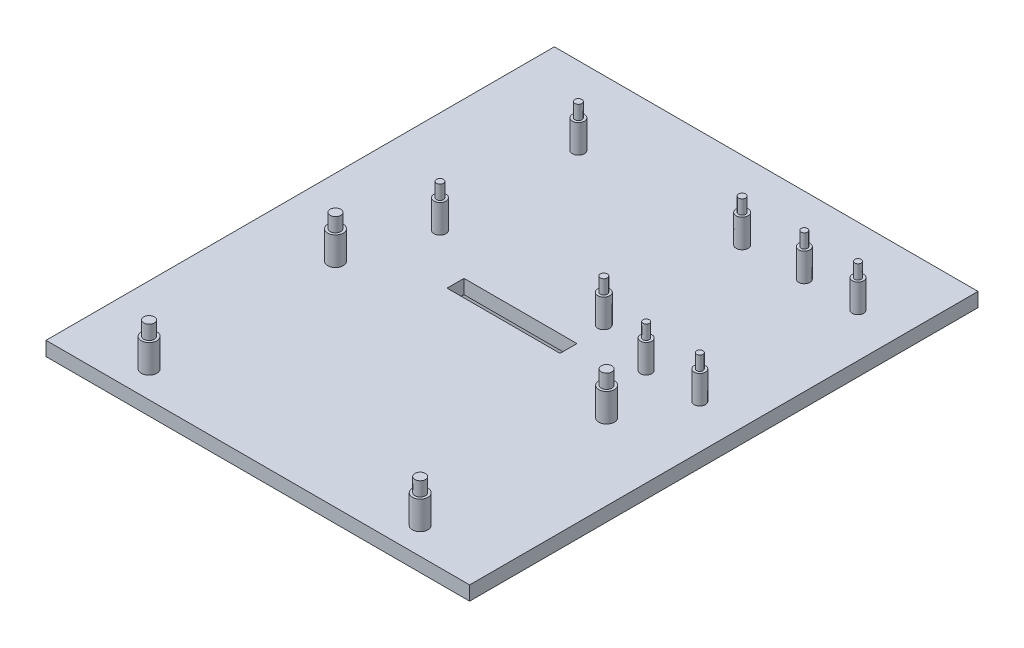
SolidWorks part; units mm, degrees
ref_plane "Front" through (0, 0, 0) normal (0, 0, 1) x (1, 0, 0)
ref_plane "Top" through (0, 0, 0) normal (0, 1, 0) x (1, 0, 0)
ref_plane "Right" through (0, 0, 0) normal (1, 0, 0) x (0, 0, -1)
sketch "Esquisse1" plane through (0, 0, 0) normal (0, 1, 0) x (1, 0, 0)
  line L1 (-31, 6) -> (31, 6)
  line L2 (-31, 6) -> (-31, -6)
  line L3 (-31, -6) -> (31, -6)
  line L4 (31, 6) -> (31, -6)
  line L5 (-31, 6) -> (31, -6) construction
  line L6 (-31, -6) -> (31, 6) construction
  line L7 (-29, 4) -> (29, 4)
  line L8 (-29, 4) -> (-29, -4)
  line L9 (-29, -4) -> (29, -4)
  line L10 (29, 4) -> (29, -4)
  line L11 (-29, 4) -> (29, -4) construction
  line L12 (-29, -4) -> (29, 4) construction
  point P0 (0, 0)
  point P6 (0, 0)
  dimension "D1" = 8
  dimension "D2" = 12
  dimension "D3" = 62
  dimension "D4" = 58
extrude "Boss.-Extru.1" add sketch "Esquisse1" along normal blind 15
sketch "Esquisse2" plane through (0, 0, 6) normal (0, 0, 1) x (1, 0, 0)
  line L0 (-31, 15) -> (31, 15) construction
  line L1 (31, 15) -> (31, 0) construction
  circle A0 centre (0, 9) radius 3.175
  dimension "D1" = 6.35
  dimension "D2" = 6
  dimension "D3" = 31
extrude "Enlèv. mat.-Extru.1" cut sketch "Esquisse2" against normal through all
sketch "Esquisse3" plane through (0, 15, 0) normal (0, 1, 0) x (1, 0, 0)
  line L1 (-75, 90) -> (75, 90)
  line L2 (-75, 90) -> (-75, -90)
  line L3 (-75, -90) -> (75, -90)
  line L4 (75, 90) -> (75, -90)
  line L5 (-75, 90) -> (75, -90) construction
  line L6 (-75, -90) -> (75, 90) construction
  point P0 (0, 0)
  dimension "D1" = 180
  dimension "D2" = 150
extrude "Boss.-Extru.2" add sketch "Esquisse3" along normal blind 5
sketch "Esquisse4" plane through (0, 20, 0) normal (0, 1, 0) x (1, 0, 0)
  line L0 (75, -90) -> (75, 90) construction
  line L1 (-52.5, -85) -> (52.5, -85) construction
  line L2 (-52.5, -85) -> (-52.5, -10) construction
  line L3 (-52.5, -10) -> (52.5, -10) construction
  line L4 (52.5, -85) -> (52.5, -10) construction
  line L5 (-52.5, -85) -> (52.5, -10) construction
  line L6 (-52.5, -10) -> (52.5, -85) construction
  line L7 (-75, -90) -> (75, -90) construction
  line L9 (-61.5, 10) -> (22.5, 10) construction
  line L10 (-61.5, 10) -> (-61.5, 66) construction
  line L11 (-61.5, 66) -> (22.5, 66) construction
  line L12 (22.5, 10) -> (22.5, 66) construction
  line L13 (-61.5, 10) -> (22.5, 66) construction
  line L14 (-61.5, 66) -> (22.5, 10) construction
  line L15 (37.5, 4) -> (62.5, 4) construction
  line L16 (37.5, 4) -> (37.5, 66) construction
  line L17 (37.5, 66) -> (62.5, 66) construction
  line L18 (62.5, 4) -> (62.5, 66) construction
  line L19 (37.5, 4) -> (62.5, 66) construction
  line L20 (37.5, 66) -> (62.5, 4) construction
  line L21 (75, 90) -> (-75, 90) construction
  point P4 (0, -47.5)
  point P10 (0, -90)
  point P15 (-19.5, 38)
  point P21 (50, 35)
  point P22 (75, 0)
  point P23 (41.9956, 9.0728)
  point P24 (0, 90)
  dimension "D1" = 75
  dimension "D2" = 105
  dimension "D3" = 10
  dimension "D4" = 56
  dimension "D5" = 84
  dimension "D6" = 15
  dimension "D7" = 62
  dimension "D8" = 25
  dimension "D9" = 22.5
  dimension "D10" = 10
sketch "Esquisse6" plane through (0, 15, 0) normal (0, -1, 0) x (-1, 0, 0)
  line L0 (-29, -4) -> (-29, 4) construction
  line L1 (20, 3) -> (-20, 3)
  line L2 (20, 3) -> (20, -3)
  line L3 (20, -3) -> (-20, -3)
  line L4 (-20, 3) -> (-20, -3)
  line L5 (20, 3) -> (-20, -3) construction
  line L6 (20, -3) -> (-20, 3) construction
  line L7 (29, -4) -> (-29, -4) construction
  point P4 (0, 0)
  point P8 (-29, 0)
  point P12 (0, -4)
  dimension "D1" = 6
  dimension "D2" = 40
extrude "Enlèv. mat.-Extru.3" cut sketch "Esquisse6" against normal up to next
sketch "Esquisse8" plane through (0, 20, 0) normal (0, 1, 0) x (1, 0, 0)
  line L0 (-61.5, 66) -> (22.5, 66) construction
  line L1 (22.5, 10) -> (22.5, 66) construction
  circle A0 centre (19, 62.5) radius 1.25
  circle A1 centre (19, 13.5) radius 1.25
  circle A2 centre (-39, 62.5) radius 1.25
  circle A3 centre (-39, 13.5) radius 1.25
  dimension "D1" = 2.5
  dimension "D4" = 2.5
  dimension "D6" = 2.5
  dimension "D8" = 2.5
  dimension "D2" = 3.5
  dimension "D3" = 3.5
  dimension "D5" = 49
  dimension "D7" = 58
sketch "Esquisse9" plane through (0, 20, 0) normal (0, 1, 0) x (1, 0, 0)
  line L0 (62.5, 4) -> (62.5, 66) construction
  line L1 (37.5, 66) -> (62.5, 66) construction
  circle A0 centre (59.5, 63) radius 1.125
  circle A1 centre (40.5, 63) radius 1.125
  circle A2 centre (59.5, 7) radius 1.125
  circle A3 centre (40.5, 7) radius 1.125
  dimension "D1" = 2.25
  dimension "D4" = 2.25
  dimension "D6" = 2.25
  dimension "D8" = 2.25
  dimension "D2" = 3
  dimension "D3" = 3
  dimension "D5" = 19
  dimension "D7" = 56
sketch "Esquisse10" plane through (0, 20, 0) normal (0, 1, 0) x (1, 0, 0)
  line L0 (-52.5, -10) -> (52.5, -10) construction
  line L1 (-52.5, -85) -> (-52.5, -10) construction
  circle A0 centre (-48, -14.5) radius 1.875
  circle A1 centre (48, -14.5) radius 1.875
  circle A2 centre (-48, -80.5) radius 1.875
  circle A3 centre (48, -80.5) radius 1.875
  dimension "D1" = 3.75
  dimension "D4" = 3.75
  dimension "D6" = 3.75
  dimension "D8" = 3.75
  dimension "D2" = 4.5
  dimension "D3" = 4.5
  dimension "D5" = 96
  dimension "D7" = 66
sketch "Esquisse11" plane through (0, 20, 0) normal (0, 1, 0) x (1, 0, 0)
  line L0 (-52.5, -10) -> (52.5, -10) construction
  line L1 (-52.5, -85) -> (-52.5, -10) construction
  circle A0 centre (-48, -14.5) radius 2.75
  circle A1 centre (-48, -80.5) radius 2.75
  circle A2 centre (48, -14.5) radius 2.75
  circle A3 centre (48, -80.5) radius 2.75
  dimension "D3" = 5.5
  dimension "D5" = 5.5
  dimension "D6" = 96
  dimension "D7" = 5.5
  dimension "D8" = 5.5
  dimension "D1" = 4.5
  dimension "D2" = 4.5
  dimension "D4" = 66
sketch "Esquisse12" plane through (0, 20, 0) normal (0, 1, 0) x (1, 0, 0)
  line L0 (-61.5, 66) -> (22.5, 66) construction
  line L1 (22.5, 10) -> (22.5, 66) construction
  circle A0 centre (19, 62.5) radius 2.125
  circle A1 centre (19, 13.5) radius 2.125
  circle A2 centre (-39, 62.5) radius 2.125
  circle A3 centre (-39, 13.5) radius 2.125
  dimension "D3" = 4.25
  dimension "D5" = 4.25
  dimension "D7" = 4.25
  dimension "D8" = 4.25
  dimension "D1" = 3.5
  dimension "D2" = 3.5
  dimension "D4" = 49
  dimension "D6" = 58
sketch "Esquisse13" plane through (0, 20, 0) normal (0, 1, 0) x (1, 0, 0)
  line L0 (37.5, 4) -> (62.5, 4) construction
  line L1 (62.5, 4) -> (62.5, 66) construction
  circle A0 centre (59.5, 7) radius 2
  circle A1 centre (59.5, 63) radius 2
  circle A2 centre (40.5, 7) radius 2
  circle A3 centre (40.5, 63) radius 2
  dimension "D3" = 4
  dimension "D4" = 4
  dimension "D6" = 4
  dimension "D8" = 4
  dimension "D1" = 3
  dimension "D2" = 3
  dimension "D5" = 56
  dimension "D7" = 19
extrude "Boss.-Extru.3" add sketch "Esquisse11" along normal blind 10
extrude "Boss.-Extru.4" add sketch "Esquisse13" along normal blind 10
extrude "Boss.-Extru.5" add sketch "Esquisse12" along normal blind 10
extrude "Boss.-Extru.6" add sketch "Esquisse10" along normal blind 15
extrude "Boss.-Extru.7" add sketch "Esquisse9" along normal blind 15
extrude "Boss.-Extru.8" add sketch "Esquisse8" along normal blind 15
